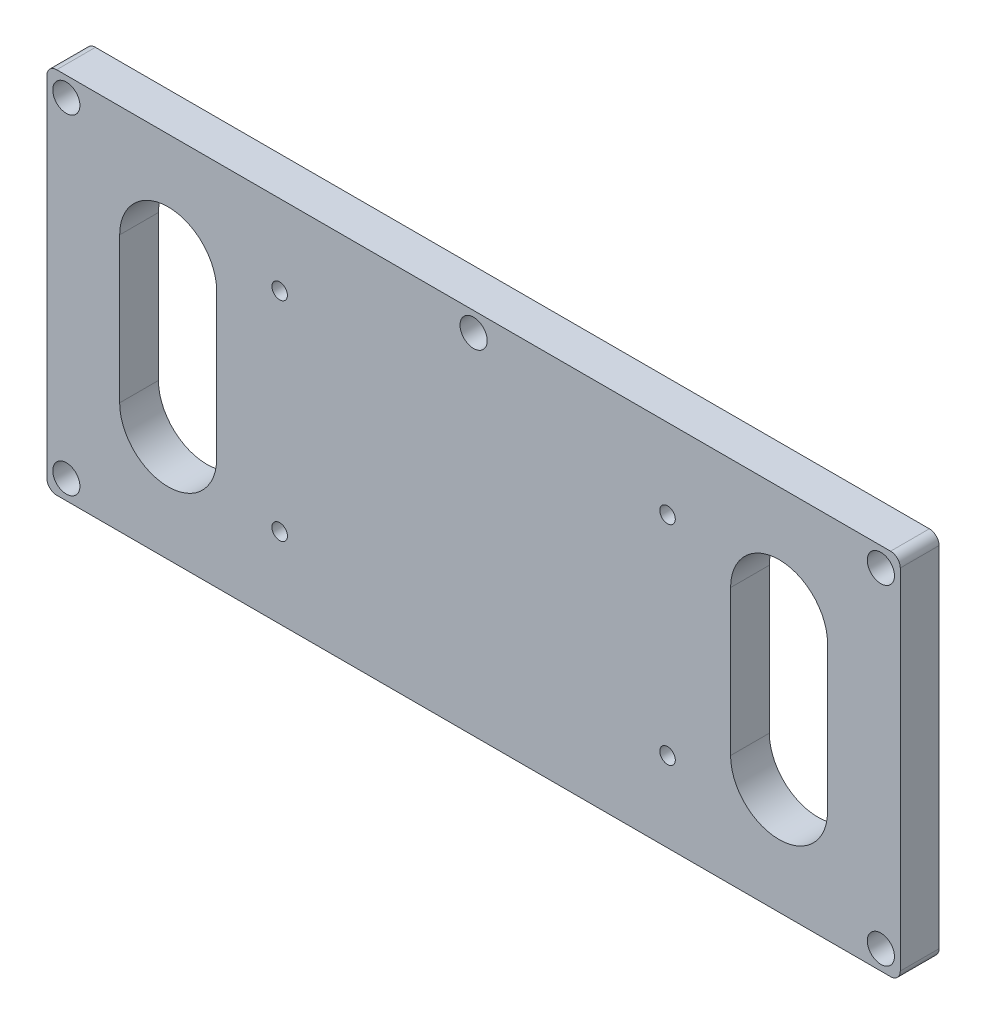
SolidWorks part; units mm, degrees
material "PETG-HF"
ref_plane "前视基准面" through (0, 0, 0) normal (0, 0, 1) x (1, 0, 0)
ref_plane "上视基准面" through (0, 0, 0) normal (0, 1, 0) x (1, 0, 0)
ref_plane "右视基准面" through (0, 0, 0) normal (1, 0, 0) x (0, 0, -1)
other "Configuration Table"
sketch "草图1" plane through (0, 0, 0) normal (0, 0, 1) x (1, 0, 0)
  line L1 (88, -38) -> (-88, -38)
  line L2 (88, -38) -> (88, 38)
  line L3 (88, 38) -> (-88, 38)
  line L4 (-88, -38) -> (-88, 38)
  line L5 (88, -38) -> (-88, 38) construction
  line L6 (88, 38) -> (-88, -38) construction
  point P0 (0, 0)
  dimension "D1" = 176
  dimension "D2" = 76
extrude "凸台-拉伸1" add sketch "草图1" along normal blind 8
sketch "草图2" plane through (0, 0, 0) normal (0, 0, -1) x (-1, 0, 0)
  line L0 (-88, -38) -> (-88, 38) construction
  line L1 (-88, 38) -> (88, 38) construction
  line L2 (88, -38) -> (-88, -38) construction
  line L3 (88, 38) -> (88, -38) construction
  circle A0 centre (-84, 34) radius 1.6
  circle A1 centre (-84, -34) radius 1.6
  circle A2 centre (-84, 0) radius 2.6
  circle A3 centre (0, 34) radius 1.6
  circle A4 centre (84, 34) radius 1.6
  circle A5 centre (84, 0) radius 2.6
  circle A6 centre (84, -34) radius 1.6
  circle A7 centre (0, -34) radius 2.6
  point P28 (0, 38)
  point P29 (-88, 0)
  dimension "D1" = 3.2
  dimension "D2" = 5.2
  dimension "D3" = 3.2
  dimension "D4" = 3.2
  dimension "D5" = 3.2
  dimension "D6" = 5.2
  dimension "D7" = 5.2
  dimension "D8" = 3.2
  dimension "D9" = 4
  dimension "D10" = 4
  dimension "D11" = 4
  dimension "D12" = 4
extrude "切除-拉伸1" cut sketch "草图2" against normal through all contours A0 | A3 | A4 | A1 | A6 region at (84, 34, 0) region at (0, 34, 0) region at (-84, 34, 0)
extrude "切除-拉伸2" cut sketch "草图2<3>" against normal blind 3 contours A2 | A7 | A5
sketch "草图2<3>" plane through (0, 0, 0) normal (0, 0, -1) x (-1, 0, 0) same geometry as "草图2"
sketch "草图4" plane through (0, 0, 8) normal (0, 0, 1) x (1, 0, 0)
  circle A0 centre (-84, 34) radius 2.8
  circle A1 centre (0, 34) radius 2.8
  circle A2 centre (-84, -34) radius 2.8
  circle A3 centre (84, 34) radius 2.8
  circle A4 centre (84, -34) radius 2.8
  dimension "D1" = 5.6
extrude "切除-拉伸3" cut sketch "草图4" against normal blind 4
fillet "圆角1" radius 2 4 edges at (88, 38, 4) (88, -38, 4) (-88, -38, 4) (-88, 38, 4)
sketch "Sketch1" plane through (0, 0, 8) normal (0, 0, 1) x (1, 0, 0)
  line L0 (86, 38) -> (-86, 38) construction
  line L1 (-40, 21.5) -> (40, 21.5) construction
  line L2 (-40, 21.5) -> (-40, -21.5) construction
  line L3 (-40, -21.5) -> (40, -21.5) construction
  line L4 (40, 21.5) -> (40, -21.5) construction
  line L5 (-88, 36) -> (-88, -36) construction
  line L6 (-40, 0) -> (40, 0) construction
  line L7 (0, 21.5) -> (0, -21.5) construction
  circle A0 centre (-40, 21.5) radius 1.6
  circle A1 centre (40, 21.5) radius 1.6
  circle A2 centre (40, -21.5) radius 1.6
  circle A3 centre (-40, -21.5) radius 1.6
  point P6 (0, 38)
  point P7 (0, 21.5)
  point P10 (-88, 0)
  point P11 (-40, 0)
  dimension "D3" = 3.2
  dimension "D1" = 80
  dimension "D2" = 43
extrude "Cut-Extrude1" cut sketch "Sketch1" against normal through all
sketch "Sketch2" plane through (0, 0, 0) normal (0, 0, -1) x (-1, 0, 0)
  line L0 (0, 21.5) -> (0, -21.5) construction
  line L1 (-40, 0) -> (40, 0) construction
  line L2 (40, 21.5) -> (40, -21.5) construction
  circle A0 centre (-40, 21.5) radius 3
  circle A2 centre (40, 21.5) radius 3
  circle A3 centre (40, -21.5) radius 3
  circle A4 centre (-40, -21.5) radius 3
  dimension "D1" = 6
extrude "Cut-Extrude2" cut sketch "Sketch2" against normal blind 4
sketch "Sketch3" plane through (0, 0, 8) normal (0, 0, 1) x (1, 0, 0)
  line L0 (-63, -15) -> (-63, 15) construction
  line L1 (-73, -15) -> (-73, 15)
  line L2 (-53, -15) -> (-53, 15)
  line L3 (-88, 36) -> (-88, -36) construction
  line L4 (0, 21.5) -> (0, -21.5) construction
  line L5 (63, -15) -> (63, 15) construction
  line L6 (73, -15) -> (73, 15)
  line L7 (53, -15) -> (53, 15)
  arc A0 (-73, -15) -> (-53, -15) centre (-63, -15) ccw
  arc A1 (-53, 15) -> (-73, 15) centre (-63, 15) ccw
  arc A2 (73, -15) -> (53, -15) centre (63, -15) cw
  arc A3 (53, 15) -> (73, 15) centre (63, 15) cw
  point P2 (-63, 0)
  point P9 (-88, 0)
  point P10 (-63, 25)
  point P11 (-63, -25)
  point P18 (63, 0)
  dimension "D1" = 20
  dimension "D2" = 25
  dimension "D3" = 50
extrude "Cut-Extrude3" cut sketch "Sketch3" against normal through all
